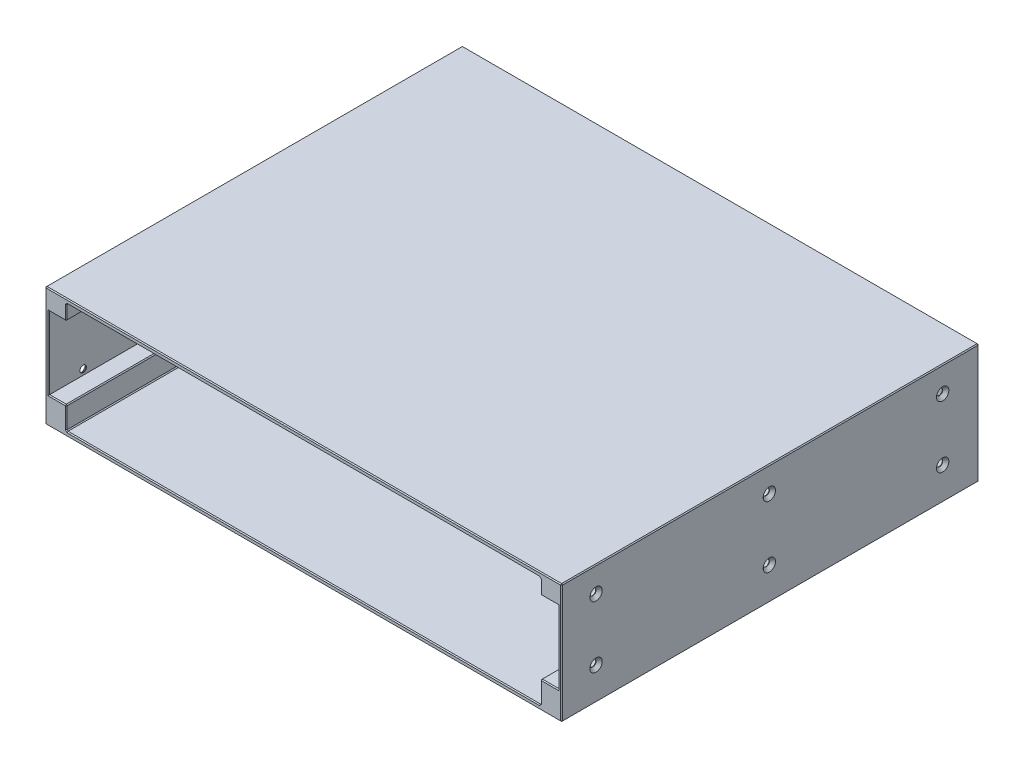
SolidWorks part; units mm, degrees
ref_plane "Front" through (0, 0, 0) normal (0, 0, 1) x (1, 0, 0)
ref_plane "Top" through (0, 0, 0) normal (0, 1, 0) x (1, 0, 0)
ref_plane "Right" through (0, 0, 0) normal (1, 0, 0) x (0, 0, -1)
sketch "Sketch1" plane through (0, 0, 0) normal (0, 0, 1) x (1, 0, 0)
  line L1 (-138, -30) -> (138, -30)
  line L2 (-138, -30) -> (-138, 30)
  line L3 (-138, 30) -> (138, 30)
  line L4 (138, -30) -> (138, 30)
  line L5 (-138, -30) -> (138, 30) construction
  line L6 (-138, 30) -> (138, -30) construction
  point P0 (0, 0)
  dimension "D1" = 276
  dimension "D2" = 60
extrude "Walls" add sketch "Sketch1" along normal blind 225 thin thin type one direction wall 2.5
sketch "Sketch2" plane through (0, 0, 0) normal (0, 0, 1) x (1, 0, 0)
  line L12 (140.5, -32.5) -> (140.5, 32.5)
  line L13 (140.5, 32.5) -> (-140.5, 32.5)
  line L14 (-140.5, 32.5) -> (-140.5, -32.5)
  line L15 (-140.5, -32.5) -> (140.5, -32.5)
  line L16 (140.5, -32.5) -> (140.5, 32.5)
  line L17 (140.5, 32.5) -> (-140.5, 32.5)
  line L18 (-140.5, 32.5) -> (-140.5, -32.5)
  line L19 (-140.5, -32.5) -> (140.5, -32.5)
  dimension "D1" = 0
extrude "Back Plate" add sketch "Sketch2" against normal blind 2
sketch "Sketch7" plane through (138.5, 0, 0) normal (1, 0, 0) x (0, 0, -1)
  line L0 (0, -30) -> (0, 30) construction
  line L1 (0, -17.75) -> (-225, -17.75)
  line L2 (0, -17.75) -> (0, 21.75)
  line L3 (0, 21.75) -> (-225, 21.75)
  line L4 (-225, -17.75) -> (-225, 21.75)
  line L5 (-225, -32.5) -> (-225, 32.5) construction
extrude "Drawer Slide Pocket" cut sketch "Sketch7" against normal up to next
sketch "Sketch8" plane through (138, 0, 0) normal (-1, 0, 0) x (0, 0, 1)
  line L0 (225, 32.5) -> (225, -32.5) construction
  line L1 (0, -30) -> (225, -30)
  line L2 (0, -30) -> (0, -17.75)
  line L3 (0, -17.75) -> (225, -17.75)
  line L4 (225, -30) -> (225, -17.75)
  line L6 (0, 30) -> (225, 30)
  line L7 (0, 30) -> (0, 21.75)
  line L8 (0, 21.75) -> (225, 21.75)
  line L9 (225, 30) -> (225, 21.75)
extrude "Drawer Slide Brackets" add sketch "Sketch8" along normal blind 9
sketch "Sketch9" plane through (140.5, 0, 0) normal (1, 0, 0) x (0, 0, -1)
  point P0 (-206.2857, -14.75)
  point P1 (-206.2857, 18.75)
  point P3 (-112, -14.75)
  point P5 (-112, 18.75)
  point P7 (-17.7143, -14.75)
  point P9 (-17.7143, 18.75)
hole_wizard "CSK for M3 SFHCS1" positions "Sketch9" profile "Sketch10" countersink size "M3" standard "ANSI Metric" end condition up to next
sketch "Sketch10" plane through (140.5, -14.75, 206.2857) normal (0, 1, 0) x (0, 0, -1)
  line L0 (0, 0) -> (0, 2)
  line L1 (0, 2) -> (1.8, 2)
  line L2 (1.7, 1.9) -> (1.7, 1.66)
  line L3 (1.7, 1.66) -> (3.36, 0)
  line L5 (3.36, 0) -> (0, 0)
  line L6 (-1.7, 1.66) -> (-3.36, 0) construction
  line L7 (1.8, 2) -> (1.7, 1.9)
  line L8 (-1.8, 2) -> (-1.7, 1.9) construction
  line L11 (0, -6.35) -> (0, 107.95) construction
  dimension "Thru Hole Dia." = 3.4
  dimension "Thru Hole Depth" = 2
  dimension "Near C'Sink Dia." = 6.72
  dimension "Near C'Sink Angle" = 90
  dimension "Far C'Sink Dia." = 3.6
  dimension "Far C'Sink Angle" = 90
mirror "Drawer Slide Pocket mirror" about plane through (0, 0, 0) normal (1, 0, 0) of "CSK for M3 SFHCS1", "Drawer Slide Pocket", "Drawer Slide Brackets"
sketch "Sketch3" plane through (0, -32.5, 0) normal (0, 1, 0) x (1, 0, 0)
  line L0 (0, 2) -> (0, -111.5) construction
  line L1 (-114.5192, -23.9808) -> (114.5192, -23.9808) construction
  line L2 (-114.5192, -23.9808) -> (-114.5192, -199.0192) construction
  line L3 (-114.5192, -199.0192) -> (114.5192, -199.0192) construction
  line L4 (114.5192, -23.9808) -> (114.5192, -199.0192) construction
  line L5 (-114.5192, -23.9808) -> (114.5192, -199.0192) construction
  line L6 (-114.5192, -199.0192) -> (114.5192, -23.9808) construction
  line L8 (0, -111.5) -> (0, -225) construction
  line L10 (-140.5, -23.9808) -> (-114.5192, -23.9808) construction
  line L11 (140.5, 2) -> (-140.5, 2) construction
  line L12 (-114.5192, -23.9808) -> (-114.5192, 2) construction
  line L13 (-57.2596, -23.9808) -> (-57.2596, -15.3205) construction
  line L14 (-114.5192, -32.641) -> (-107.0192, -28.3109)
  line L15 (-107.0192, -28.3109) -> (-107.0192, -19.6506)
  line L16 (-107.0192, -19.6506) -> (-114.5192, -15.3205)
  line L17 (-114.5192, -15.3205) -> (-122.0192, -19.6506)
  line L18 (-122.0192, -19.6506) -> (-122.0192, -28.3109)
  line L19 (-122.0192, -28.3109) -> (-114.5192, -32.641)
  line L20 (-57.2596, -15.3205) -> (-57.2596, -6.6603) construction
  line L21 (0, -111.5) -> (114.5192, -111.5) construction
  line L22 (122.0192, -28.3109) -> (114.5192, -32.641)
  line L23 (122.0192, -19.6506) -> (122.0192, -28.3109)
  line L24 (114.5192, -15.3205) -> (122.0192, -19.6506)
  line L25 (107.0192, -19.6506) -> (114.5192, -15.3205)
  line L26 (107.0192, -28.3109) -> (107.0192, -19.6506)
  line L27 (114.5192, -32.641) -> (107.0192, -28.3109)
  line L28 (122.0192, -203.3494) -> (122.0192, -194.6891)
  line L29 (114.5192, -207.6795) -> (122.0192, -203.3494)
  line L30 (107.0192, -203.3494) -> (114.5192, -207.6795)
  line L31 (107.0192, -194.6891) -> (107.0192, -203.3494)
  line L32 (114.5192, -190.359) -> (107.0192, -194.6891)
  line L33 (122.0192, -194.6891) -> (114.5192, -190.359)
  line L34 (-122.0192, -194.6891) -> (-114.5192, -190.359)
  line L35 (-122.0192, -203.3494) -> (-122.0192, -194.6891)
  line L36 (-114.5192, -207.6795) -> (-122.0192, -203.3494)
  line L37 (-107.0192, -203.3494) -> (-114.5192, -207.6795)
  line L38 (-107.0192, -194.6891) -> (-107.0192, -203.3494)
  line L39 (-114.5192, -190.359) -> (-107.0192, -194.6891)
  line L40 (-57.2596, -6.6603) -> (-57.2596, 2) construction
  line L41 (-114.5192, -10.9904) -> (-57.2596, -10.9904) construction
  line L42 (-57.2596, -10.9904) -> (0, -10.9904) construction
  line L43 (-140.5, -225) -> (-140.5, 2) construction
  line L44 (140.5, -225) -> (-140.5, -225) construction
  circle A0 centre (-114.5192, -23.9808) radius 7.5 construction
  point P0 (0, -111.5)
  dimension "D1" = 15
extrude "Foot Pocket" cut sketch "Sketch3" along normal blind 1.5 draft 45
sketch "Sketch4" plane through (0, 32.5, 0) normal (0, -1, 0) x (1, 0, 0)
  line L20 (-107.2192, 203.2339) -> (-114.5192, 207.4486)
  line L21 (-114.5192, 207.4486) -> (-121.8192, 203.2339)
  line L22 (-121.8192, 203.2339) -> (-121.8192, 194.8046)
  line L23 (-121.8192, 194.8046) -> (-114.5192, 190.5899)
  line L24 (-114.5192, 190.5899) -> (-107.2192, 194.8046)
  line L25 (-107.2192, 194.8046) -> (-107.2192, 203.2339)
  line L26 (-107.2192, 203.2339) -> (-114.5192, 207.4486)
  line L27 (-114.5192, 207.4486) -> (-121.8192, 203.2339)
  line L28 (-121.8192, 203.2339) -> (-121.8192, 194.8046)
  line L29 (-121.8192, 194.8046) -> (-114.5192, 190.5899)
  line L30 (-114.5192, 190.5899) -> (-107.2192, 194.8046)
  line L31 (-107.2192, 194.8046) -> (-107.2192, 203.2339)
  line L38 (-114.5192, 32.4101) -> (-121.8192, 28.1954)
  line L39 (-121.8192, 28.1954) -> (-121.8192, 19.7661)
  line L40 (-121.8192, 19.7661) -> (-114.5192, 15.5514)
  line L41 (-114.5192, 15.5514) -> (-107.2192, 19.7661)
  line L42 (-107.2192, 19.7661) -> (-107.2192, 28.1954)
  line L43 (-107.2192, 28.1954) -> (-114.5192, 32.4101)
  line L44 (-114.5192, 32.4101) -> (-121.8192, 28.1954)
  line L45 (-121.8192, 28.1954) -> (-121.8192, 19.7661)
  line L46 (-121.8192, 19.7661) -> (-114.5192, 15.5514)
  line L47 (-114.5192, 15.5514) -> (-107.2192, 19.7661)
  line L48 (-107.2192, 19.7661) -> (-107.2192, 28.1954)
  line L49 (-107.2192, 28.1954) -> (-114.5192, 32.4101)
  line L56 (114.5192, 207.4486) -> (107.2192, 203.2339)
  line L57 (107.2192, 203.2339) -> (107.2192, 194.8046)
  line L58 (107.2192, 194.8046) -> (114.5192, 190.5899)
  line L59 (114.5192, 190.5899) -> (121.8192, 194.8046)
  line L60 (121.8192, 194.8046) -> (121.8192, 203.2339)
  line L61 (121.8192, 203.2339) -> (114.5192, 207.4486)
  line L62 (114.5192, 207.4486) -> (107.2192, 203.2339)
  line L63 (107.2192, 203.2339) -> (107.2192, 194.8046)
  line L64 (107.2192, 194.8046) -> (114.5192, 190.5899)
  line L65 (114.5192, 190.5899) -> (121.8192, 194.8046)
  line L66 (121.8192, 194.8046) -> (121.8192, 203.2339)
  line L67 (121.8192, 203.2339) -> (114.5192, 207.4486)
  line L74 (121.8192, 19.7661) -> (121.8192, 28.1954)
  line L75 (114.5192, 15.5514) -> (121.8192, 19.7661)
  line L76 (107.2192, 19.7661) -> (114.5192, 15.5514)
  line L77 (107.2192, 28.1954) -> (107.2192, 19.7661)
  line L78 (114.5192, 32.4101) -> (107.2192, 28.1954)
  line L79 (121.8192, 28.1954) -> (114.5192, 32.4101)
  line L80 (121.8192, 19.7661) -> (121.8192, 28.1954)
  line L81 (114.5192, 15.5514) -> (121.8192, 19.7661)
  line L82 (107.2192, 19.7661) -> (114.5192, 15.5514)
  line L83 (107.2192, 28.1954) -> (107.2192, 19.7661)
  line L84 (114.5192, 32.4101) -> (107.2192, 28.1954)
  line L85 (121.8192, 28.1954) -> (114.5192, 32.4101)
  dimension "D1" = 0.2
  dimension "D2" = 0.2
  dimension "D3" = 0.2
  dimension "D4" = 0.2
extrude "Feet" [suppressed] add sketch "Sketch4" against normal blind 1.3 draft 45
chamfer "Deburs 1" distance 0.5 angle 45 34 edges at (-138.5, 2, 225) (-133.75, -17.75, 225) (-129, -17.75, 112.5) (-129, -23.875, 225) (0, -30, 225) (0, 30, 225) (-133.75, 21.75, 225) (-129, 21.75, 112.5) (-129, 25.875, 225) (-129, 30, 112.5) (0, 30, 0) (129, 30, 112.5) (129, 25.875, 225) (129, 21.75, 112.5) (133.75, 21.75, 225) (138.5, 2, 225) (133.75, -17.75, 225) (129, -17.75, 112.5) (129, -23.875, 225) (-129, -30, 112.5) (0, -30, 0) (129, -30, 112.5) (140.5, 0, 225) (0, -32.5, 225) (-140.5, 0, 225) (0, 32.5, 225) (-140.5, 0, -2) (-140.5, 32.5, 111.5) (0, 32.5, -2) (140.5, 32.5, 111.5) (140.5, 0, -2) (140.5, -32.5, 111.5) (0, -32.5, -2) (-140.5, -32.5, 111.5)
chamfer "Deburs 2" distance 0.5 angle 45 4 edges at (129, -23.875, 0) (129, 25.875, 0) (-129, 25.875, 0) (-129, -23.875, 0)
hole_wizard "CSK for #6 Flat Head Socket Cap Screw3" positions "Sketch11" profile "Sketch13" countersink size "#6" standard "ANSI Inch" end condition through all
sketch "Sketch11" plane through (0, 0, 0) normal (0, 0, 1) x (1, 0, 0)
  line L0 (-92, 0) -> (-46, 0) construction
  line L1 (-46, 0) -> (0, 0) construction
  line L3 (-138, 0) -> (-92, 0) construction
  line L4 (-138, -30) -> (-138, 30) construction
  line L6 (0, 0) -> (46, 0) construction
  line L7 (46, 0) -> (92, 0) construction
  point P0 (-92, 0)
  point P2 (92, 0)
sketch "Sketch13" plane through (-92, 0, 0) normal (1, 0, 0) x (0, -1, 0)
  line L0 (0, 0) -> (0, 2)
  line L1 (0, 2) -> (1.8986, 2)
  line L2 (1.8986, 2) -> (1.8986, 2.301)
  line L3 (1.8986, 2.301) -> (3.8989, 0)
  line L5 (3.8989, 0) -> (0, 0)
  line L6 (-1.8986, 2.301) -> (-3.8989, 0) construction
  line L11 (0, -6.35) -> (0, 107.95) construction
  dimension "Thru Hole Dia." = 3.7973
  dimension "Thru Hole Depth" = 2
  dimension "Near C'Sink Dia." = 7.7978
  dimension "Near C'Sink Angle" = 82
